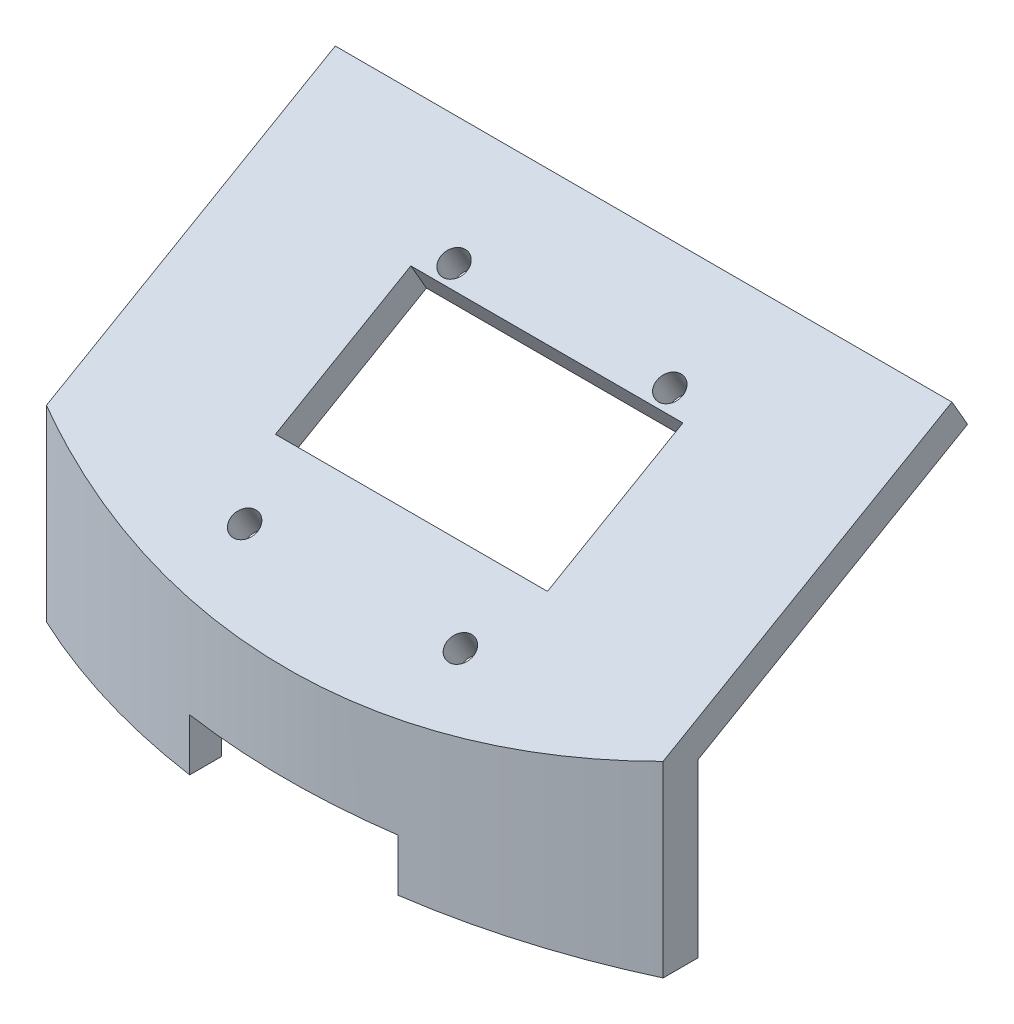
SolidWorks part; units mm, degrees
ref_plane "Front Plane" through (0, 0, 0) normal (0, 0, 1) x (1, 0, 0)
ref_plane "Top Plane" through (0, 0, 0) normal (0, 1, 0) x (1, 0, 0)
ref_plane "Right Plane" through (0, 0, 0) normal (1, 0, 0) x (0, 0, -1)
sketch "Sketch1" plane through (0, 0, 0) normal (0, 1, 0) x (1, 0, 0)
  line L0 (0, 0) -> (0, 50000) construction
  line L1 (0, 0) -> (-29.5833, -63.4415) construction
  line L2 (29.5833, -63.4415) -> (0, 0) construction
  line L5 (-29.5833, -63.4415) -> (-29.5833, -60.1151)
  line L6 (29.5833, -63.4415) -> (29.5833, -60.1151)
  arc A0 (-29.5833, -63.4415) -> (29.5833, -63.4415) centre (0, 0) ccw
  arc A1 (-29.5833, -60.1151) -> (29.5833, -60.1151) centre (0, 0) ccw
  dimension "D3" = 70
  dimension "D5" = 67
  dimension "D1" = 25
  dimension "D2" = 25
extrude "Boss-Extrude1" add sketch "Sketch1" along normal blind 18
sketch "Sketch2" plane through (0, 0, 0) normal (1, 0, 0) x (0, 0, -1)
  line L0 (-94.6185, 0) -> (-70, 14.2135)
  line L1 (0, 0) -> (-50000, 0) construction
  line L2 (-70, 18) -> (-70, 0) construction
  line L3 (-70, 14.2135) -> (-63.4415, 18) construction
  dimension "D1" = 30
ref_plane "Plane1" through (0, 40.971, 23.6546) normal (0, -0.866, -0.5) x (-1, 0, 0)
sketch "Sketch3" plane through (0, 40.971, 23.6546) normal (0, -0.866, -0.5) x (-1, 0, 0)
  line L0 (29.5833, -43.0612) -> (29.5833, -52.0612) construction
  line L1 (29.5833, -45.942) -> (-29.5833, -45.942) construction
  line L2 (29.5833, -45.942) -> (29.5833, -13.942)
  line L3 (29.5833, -13.942) -> (-29.5833, -13.942)
  line L4 (-29.5833, -45.942) -> (-29.5833, -13.942)
  line L6 (-29.5833, -45.942) -> (-29.5833, -53.515)
  line L7 (-29.5833, -53.515) -> (29.5833, -53.515)
  line L8 (29.5833, -45.942) -> (29.5833, -53.515)
  dimension "D1" = 32
extrude "Boss-Extrude2" add sketch "Sketch3" along normal blind 3
sketch "Sketch7" plane through (0, 0, 0) normal (1, 0, 0) x (0, 0, -1)
  line L1 (-70, 14.2135) -> (-63.4415, 18)
  line L2 (-63.4415, 18) -> (-70, 18)
  line L6 (0, 0) -> (0, 24.725) construction
  line L7 (-70, 18) -> (-70, 14.2135) construction
  line L8 (-70, 14.2135) -> (-70, 18)
extrude "Cut-Extrude3" cut sketch "Sketch7" against normal through all and the other way through all
sketch "Sketch8" plane through (0, 0, 0) normal (0, -1, 0) x (1, 0, 0)
  line L0 (29.5833, 63.4415) -> (29.5833, 60.1151) construction
  line L1 (-29.5833, 63.4415) -> (-29.5833, 71.5498)
  line L2 (-29.5833, 71.5498) -> (29.5833, 71.5498)
  line L3 (29.5833, 71.5498) -> (29.5833, 63.4415)
  arc A0 (-29.5833, 63.4415) -> (29.5833, 63.4415) centre (0, 0) cw
extrude "Cut-Extrude4" cut sketch "Sketch8" against normal through all
sketch "Sketch5" plane through (0, 40.971, 23.6546) normal (0, 0.866, 0.5) x (1, 0, 0)
  line L0 (0, -48.242) -> (0, -20.942) construction
  line L5 (-29.5833, -13.942) -> (29.5833, -13.942) construction
  line L7 (29.5408, -34.592) -> (-29.5408, -34.592) construction
  line L8 (0, -20.942) -> (0, -13.942) construction
  line L9 (-10.35, -22.992) -> (10.35, -22.992) construction
  line L10 (-10.35, -22.992) -> (-10.35, -46.192) construction
  line L11 (-13.05, -39.662) -> (13.05, -39.662)
  line L12 (-13.05, -39.662) -> (-13.05, -24.662)
  line L13 (-13.05, -24.662) -> (13.05, -24.662)
  line L14 (13.05, -39.662) -> (13.05, -24.662)
  line L15 (-13.05, -39.662) -> (13.05, -24.662) construction
  line L16 (-13.05, -24.662) -> (13.05, -39.662) construction
  line L20 (-13.65, -48.242) -> (13.65, -48.242) construction
  line L21 (-13.65, -48.242) -> (-13.65, -20.942) construction
  line L22 (-13.65, -20.942) -> (13.65, -20.942) construction
  line L23 (13.65, -48.242) -> (13.65, -20.942) construction
  line L24 (-13.65, -48.242) -> (13.65, -20.942) construction
  line L25 (-13.65, -20.942) -> (13.65, -48.242) construction
  line L27 (0, -48.242) -> (0, -49.242) construction
  circle A0 centre (-10.35, -22.992) radius 1.25
  circle A1 centre (10.35, -22.992) radius 1.25
  circle A2 centre (10.35, -46.192) radius 1.25
  circle A3 centre (-10.35, -46.192) radius 1.25
  point P0 (0, -32.162)
  point P24 (0, -34.592)
  dimension "D6" = 2.5
  dimension "D7" = 3.3
  dimension "D8" = 2.05
  dimension "D13" = 1
  dimension "D1" = 15
  dimension "D2" = 26.1
  dimension "D3" = 11.22
  dimension "D4" = 27.3
  dimension "D5" = 27.3
  dimension "D11" = 20.7
  dimension "D12" = 23.2
  dimension "D14" = 7
  dimension "D9" = 2
  dimension "D10" = 2
extrude "Cut-Extrude1" cut sketch "Sketch5" against normal blind 7
sketch "Sketch6" plane through (0, 0, 0) normal (0, 0, 1) x (1, 0, 0)
  line L1 (-10, -5) -> (10, -5)
  line L2 (-10, -5) -> (-10, 5)
  line L3 (-10, 5) -> (10, 5)
  line L4 (10, -5) -> (10, 5)
  line L5 (-10, -5) -> (10, 5) construction
  line L6 (-10, 5) -> (10, -5) construction
  point P0 (0, 0)
  dimension "D1" = 5
  dimension "D2" = 20
extrude "Cut-Extrude2" cut sketch "Sketch6" along normal through all
